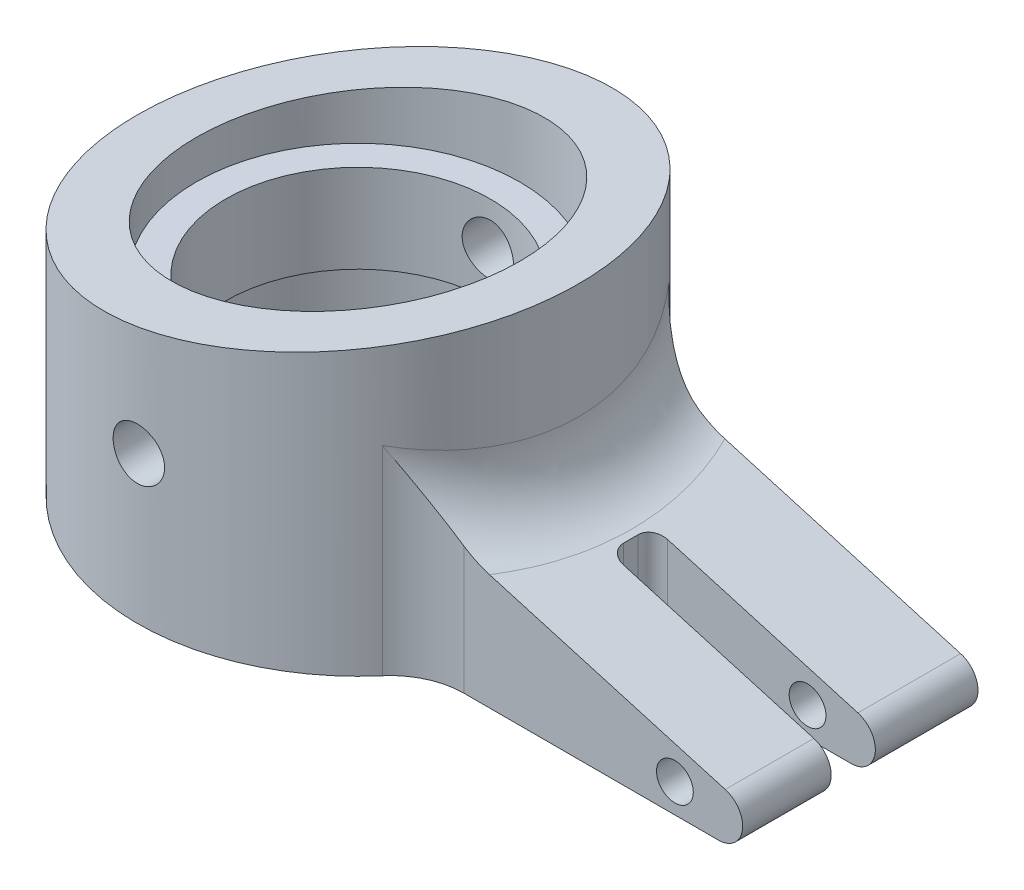
SolidWorks part; units mm, degrees
ref_plane "前视基准面" through (0, 0, 0) normal (0, 0, 1) x (1, 0, 0)
ref_plane "上视基准面" through (0, 0, 0) normal (0, 1, 0) x (1, 0, 0)
ref_plane "右视基准面" through (0, 0, 0) normal (1, 0, 0) x (0, 0, -1)
other "Configuration Table"
sketch "草图1" plane through (0, 0, 0) normal (0, 1, 0) x (1, 0, 0)
  circle A0 centre (0, 0) radius 11
  circle A1 centre (0, 0) radius 9
  circle A2 centre (0, 0) radius 15
  dimension "D1" = 22
  dimension "D2" = 18
  dimension "D3" = 30
extrude "凸台-拉伸3" add sketch "草图1" along normal blind 20 contours A2 A0 region at (-14.5757, 0, 0)
extrude "凸台-拉伸4" add sketch "草图1<7>" along normal mid plane 6 from offset 10 contours A0 A1 region at (-10.6889, 0, 0)
sketch "草图1<7>" plane through (0, 0, 0) normal (0, 1, 0) x (1, 0, 0) same geometry as "草图1"
sketch "草图6" plane through (0, 0, 0) normal (0, 0, 1) x (1, 0, 0)
  line L0 (12.5136, 0) -> (32.5136, 0)
  line L1 (32.9688, 3.2135) -> (12.5136, 9.1274)
  line L3 (12.5136, 9.1274) -> (12.5136, 0)
  arc A1 (32.5136, 0) -> (32.9688, 3.2135) centre (32.5136, 1.639) ccw
  dimension "D1" = 20
extrude "凸台-拉伸7" add sketch "草图6" along normal mid plane 16
fillet "圆角5" radius 5 1 edges at (12.6886, 4.5384, 8)
fillet "圆角6" radius 5 2 edges at (14.9606, 8.4199, 1.0869) (12.6886, 4.5384, -8)
sketch "草图8" plane through (0, 0, 0) normal (0, 1, 0) x (1, 0, 0)
  line L0 (19.0336, -1.9812) -> (37.4283, -1.9812)
  line L1 (19.0336, -1.9812) -> (19.0336, 1.0188)
  line L2 (37.4283, -1.9812) -> (37.4283, 1.0188)
  line L3 (19.0336, 1.0188) -> (37.4283, 1.0188)
  line L4 (37.4283, -0.4812) -> (19.0336, -0.4812) construction
  line L5 (28.231, -1.9812) -> (28.231, 1.0188) construction
  point P1 (28.231, -0.4812)
  dimension "D1" = 3
extrude "切除-拉伸6" cut sketch "草图8" along normal blind 16
fillet "圆角7" radius 1 1 edges at (19.0336, 3.6212, -1.0188)
fillet "圆角8" radius 1 1 edges at (19.0336, 3.6212, 1.9812)
sketch "草图9" plane through (0, 0, 0) normal (0, 0, 1) x (1, 0, 0)
  circle A0 centre (29.5445, 1.9613) radius 1.25
  dimension "D1" = 2.5
extrude "切除-拉伸7" cut sketch "草图9" against normal through all both and the other way through all
sketch "草图10" plane through (0, 0, 0) normal (0, 0, 1) x (1, 0, 0)
  line L0 (15, 20) -> (-15, 14.9506)
  line L1 (-15, 20) -> (-15, 0) construction
  line L2 (-15, 14.9506) -> (-15, 20)
  line L3 (-15, 20) -> (15, 20)
extrude "切除-拉伸8" cut sketch "草图10" against normal through all both and the other way through all
sketch "草图11" plane through (0, 0, 0) normal (0, 0, 1) x (1, 0, 0)
  circle A0 centre (0, 10) radius 1.75
  dimension "D2" = 3.5
  dimension "D1" = 10
extrude "切除-拉伸9" cut sketch "草图11" against normal through all both and the other way through all
